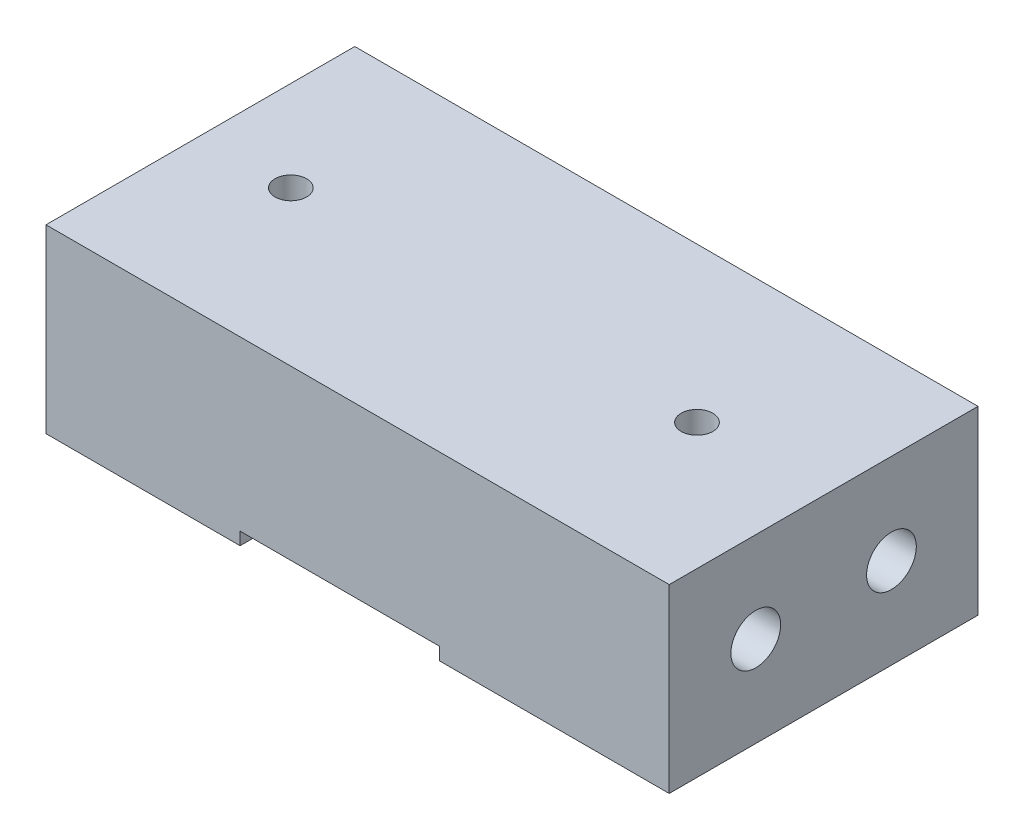
SolidWorks part; units mm, degrees
ref_plane "Front Plane" through (0, 0, 0) normal (0, 0, 1) x (1, 0, 0)
ref_plane "Top Plane" through (0, 0, 0) normal (0, 1, 0) x (1, 0, 0)
ref_plane "Right Plane" through (0, 0, 0) normal (1, 0, 0) x (0, 0, -1)
sketch "Sketch1" plane through (0, 0, 0) normal (0, 1, 0) x (1, 0, 0)
  line L1 (-34.448, 17.0677) -> (34.448, 17.0677)
  line L2 (-34.448, 17.0677) -> (-34.448, -17.0677)
  line L3 (-34.448, -17.0677) -> (34.448, -17.0677)
  line L4 (34.448, 17.0677) -> (34.448, -17.0677)
  line L5 (-34.448, 17.0677) -> (34.448, -17.0677) construction
  line L6 (-34.448, -17.0677) -> (34.448, 17.0677) construction
  point P0 (0, 0)
extrude "Boss-Extrude1" add sketch "Sketch1" along normal blind 20
sketch "Sketch2" plane through (0, 0, -17.0677) normal (0, 0, -1) x (-1, 0, 0)
  line L0 (-34.448, 0) -> (34.448, 0) construction
  line L1 (12.9895, 0) -> (-9.0428, 0)
  line L2 (12.9895, 0) -> (12.9895, 1.4)
  line L3 (12.9895, 1.4) -> (-9.0428, 1.4)
  line L4 (-9.0428, 0) -> (-9.0428, 1.4)
  dimension "D1" = 1.4
extrude "Cut-Extrude1" cut sketch "Sketch2" against normal up to next
sketch "Sketch6" plane through (34.448, 0, 0) normal (1, 0, 0) x (0, 0, -1)
  line L0 (17.0677, 10) -> (-17.0677, 10) construction
  line L1 (17.0677, 20) -> (17.0677, 0) construction
  line L2 (-17.0677, 20) -> (-17.0677, 0) construction
  circle A0 centre (7.5437, 10) radius 1.4004
  circle A1 centre (-8.7782, 10) radius 2.0081
sketch "Sketch7" plane through (34.448, 0, 0) normal (1, 0, 0) x (0, 0, -1)
  line L0 (0, 0) -> (0, 20) construction
  line L2 (-7.5, 10) -> (7.5, 10) construction
  line L3 (-17.0677, 0) -> (17.0677, 0) construction
  line L4 (-17.0677, 20) -> (17.0677, 20) construction
  circle A0 centre (-7.5, 10) radius 2.75
  circle A1 centre (7.5, 10) radius 2.75
  point P10 (0, 10)
  dimension "D1" = 5.5
  dimension "D2" = 5.5
  dimension "D3" = 15
extrude "Cut-Extrude4" cut sketch "Sketch7" against normal blind 30
sketch "Sketch8" plane through (0, 0, 0) normal (0, -1, 0) x (1, 0, 0)
  circle A0 centre (-24.448, 0) radius 1.75
  circle A1 centre (20.448, 0) radius 1.75
  dimension "D1" = 3.5
extrude "Cut-Extrude5" cut sketch "Sketch8" against normal up to next
